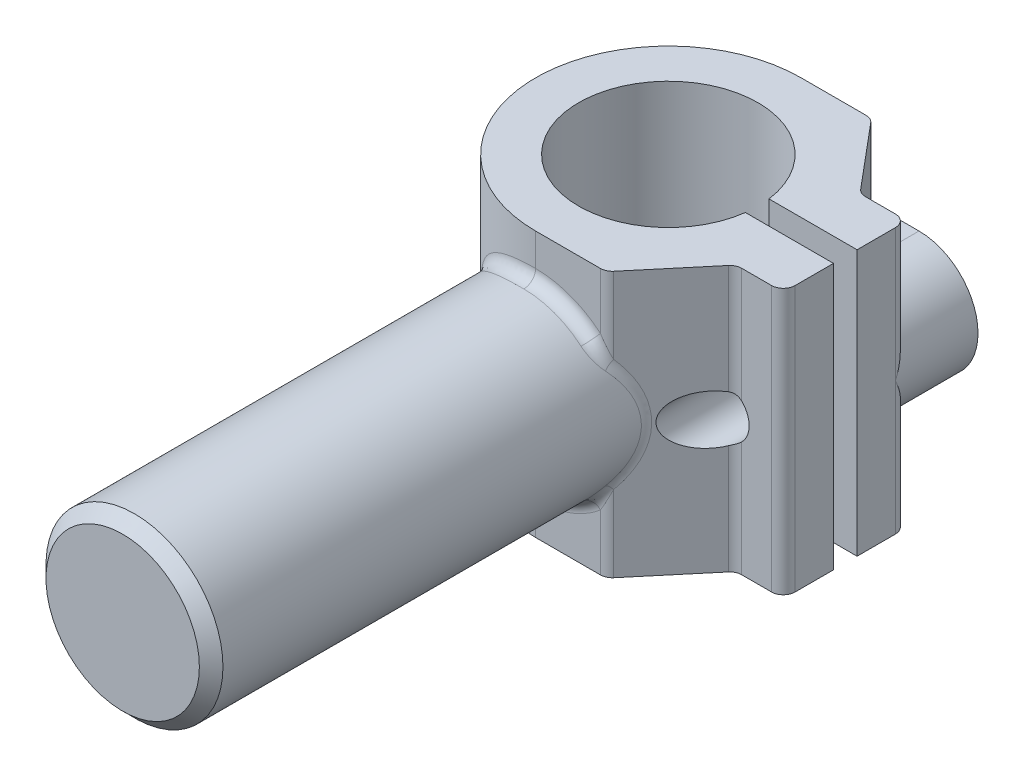
SolidWorks part; units mm, degrees
ref_plane "Front Plane" through (0, 0, 0) normal (0, 0, 1) x (1, 0, 0)
ref_plane "Top Plane" through (0, 0, 0) normal (0, 1, 0) x (1, 0, 0)
ref_plane "Right Plane" through (0, 0, 0) normal (1, 0, 0) x (0, 0, -1)
other "Configuration Table"
sketch "Sketch1" plane through (0, 0, 0) normal (0, 1, 0) x (1, 0, 0)
  line L0 (7.5339, 1) -> (15, 1)
  line L1 (0, 11.25) -> (15, 11.25)
  line L2 (7.5339, -1) -> (15, -1)
  line L3 (0, -11.25) -> (15, -11.25)
  line L4 (15, 11.25) -> (15, 1)
  line L5 (15, -1) -> (15, -11.25)
  arc A0 (7.5339, 1) -> (7.5339, -1) centre (0, 0) ccw
  arc A1 (0, 11.25) -> (0, -11.25) centre (0, 0) ccw
  dimension "D3" = 15.2
  dimension "D1" = 22.5
  dimension "D2" = 15
  dimension "D4" = 2
extrude "Extrude1" add sketch "Sketch1" along normal mid plane 22.5
sketch "Sketch4" plane through (0, 11.25, 0) normal (0, -1, 0) x (1, 0, 0)
  line L0 (15, -1) -> (15, -11.25) construction
  line L2 (5.9654, 11.25) -> (11, 5.25)
  line L3 (11, 5.25) -> (15, 5.25)
  line L5 (15, 11.25) -> (15, 5.25)
  line L7 (0, 11.25) -> (15, 11.25) construction
  line L8 (5.9654, 11.25) -> (15, 11.25)
  dimension "D1" = 4
  dimension "D2" = 130
  dimension "D3" = 6
extrude "Cut-Extrude3" cut sketch "Sketch4" along normal through all
mirror "Mirror1" about plane through (0, 0, 0) normal (0, 0, 1) of "Cut-Extrude3"
fillet "Fillet4" radius 1 6 edges at (11, 0, 5.25) (15, 0, -5.25) (11, 0, -5.25) (5.9654, 0, 11.25) (5.9654, 0, -11.25) (15, 0, 5.25)
sketch "Sketch6" plane through (0, 0, -11.25) normal (0, 0, 1) x (-1, 0, 0)
  line L0 (-15, 11.25) -> (-15, -11.25) construction
  line L1 (-10, -5) -> (0, -5)
  line L2 (0, -5) -> (0, 5)
  line L3 (0, 5) -> (-10, 5)
  arc A0 (-10, 5) -> (-10, -5) centre (-10, 0) ccw
  dimension "D1" = 5
extrude "Extrude2" add sketch "Sketch6" along normal up to next
sketch "Sketch7" plane through (0, 0, 11.25) normal (0, 0, 1) x (1, 0, 0)
  circle A0 centre (0, 0) radius 7.5
  dimension "D1" = 15
extrude "Extrude3" add sketch "Sketch7" along normal blind 35 and the other way up to next (3.65 mm away)
fillet "Fillet7" radius 1 6 edges at (5.1264, 5.4745, 9.3221) (3, 6.8739, 11.25) (-7.4891, 0.4045, 8.395) (3, -6.8739, 11.25) (5.932, -4.5893, 11.1514) (7.5, 0, 9.4211)
chamfer "Chamfer1" distance 1 angle 45 1 edges at (7.5, 0, 46.25)
hole_wizard "M5 Clearance Hole1" positions "Sketch9" profile "Sketch8" hole size "M5" standard "Ansi Metric" end condition up to next
sketch "Sketch9" plane through (0, 0, -11.25) normal (0, 0, -1) x (-1, 0, 0)
  arc A0 (-10, 5) -> (-10, -5) centre (-10, 0) ccw construction
  point P0 (-10, 0)
sketch "Sketch8" plane through (10, 0, -11.25) normal (1, 0, 0) x (0, 1, 0)
  line L0 (0, 0) -> (0, 10.25)
  line L1 (0, 10.25) -> (2.75, 10.25)
  line L2 (2.75, 10.25) -> (2.75, 0)
  line L5 (2.75, 0) -> (0, 0)
  line L11 (0, -6.35) -> (0, 107.95) construction
  dimension "Thru Hole Dia." = 5.5
  dimension "Thru Hole Depth" = 10.25
hole_wizard "M5x0.8 Tapped Hole1" positions "Sketch11" profile "Sketch10" tap size "M5x0.8" standard "Ansi Metric"
sketch "Sketch11" plane through (0, 0, 1) normal (0, 0, -1) x (-1, 0, 0)
  point P1 (-10, 0)
sketch "Sketch10" plane through (10, 0, 1) normal (1, 0, 0) x (0, 1, 0)
  line L0 (0, 0) -> (0, 13.6618)
  line L1 (0, 13.6618) -> (2.1, 12.4)
  line L2 (2.1, 12.4) -> (2.1, 0)
  line L5 (2.1, 0) -> (0, 0)
  line L10 (0, 13.6618) -> (-2.1, 12.4) construction
  line L11 (0, -6.35) -> (0, 107.95) construction
  dimension "Tap Drill Dia." = 4.2
  dimension "Tap Drill Depth" = 12.4
  dimension "Drill Angle" = 118
cosmetic thread "Hole Thread1" parameters "D1"=7.9444, "D2"=5
